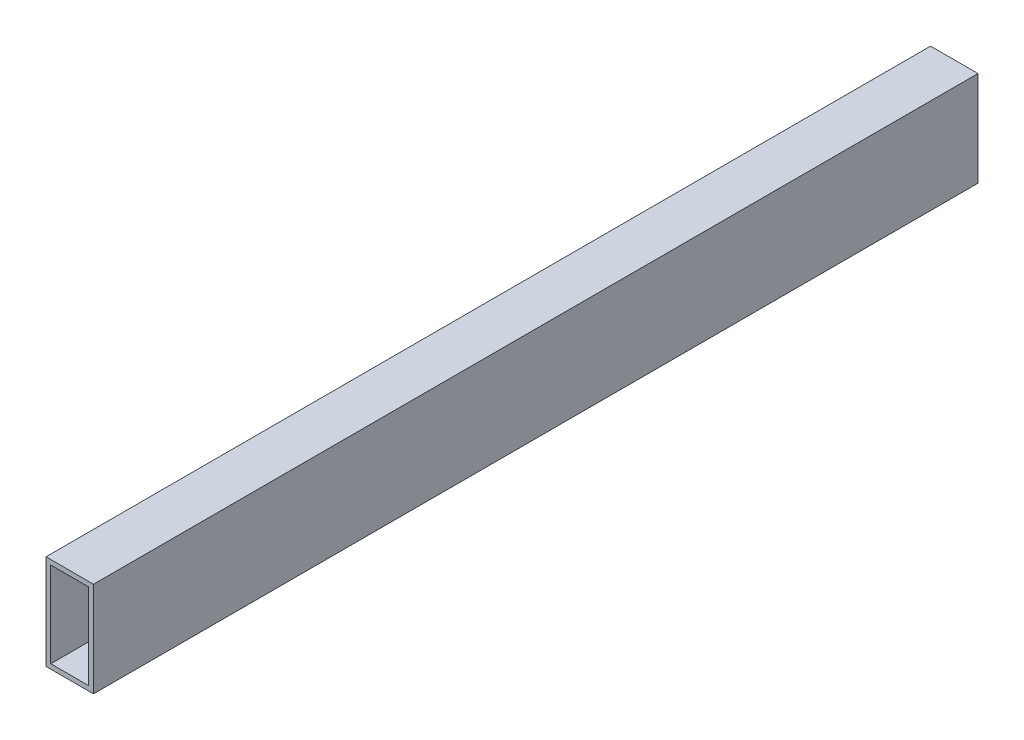
SolidWorks part; units mm, degrees
material "6061-T6 (SS)"
ref_plane "Front" through (0, 0, 0) normal (0, 0, 1) x (1, 0, 0)
ref_plane "Top" through (0, 0, 0) normal (0, 1, 0) x (1, 0, 0)
ref_plane "Right" through (0, 0, 0) normal (1, 0, 0) x (0, 0, -1)
sketch "Sketch1" plane through (0, 0, 0) normal (0, 0, 1) x (1, 0, 0)
  line L1 (-12.7, -25.4) -> (12.7, -25.4)
  line L2 (-12.7, -25.4) -> (-12.7, 25.4)
  line L3 (-12.7, 25.4) -> (12.7, 25.4)
  line L4 (12.7, -25.4) -> (12.7, 25.4)
  line L5 (-12.7, -25.4) -> (12.7, 25.4) construction
  line L6 (-12.7, 25.4) -> (12.7, -25.4) construction
  point P0 (0, 0)
  dimension "D1" = 50.8
  dimension "D2" = 25.4
extrude "Extrude-Thin1" add sketch "Sketch1" along normal blind 473.075 thin thin type one direction reverse wall 2.54
